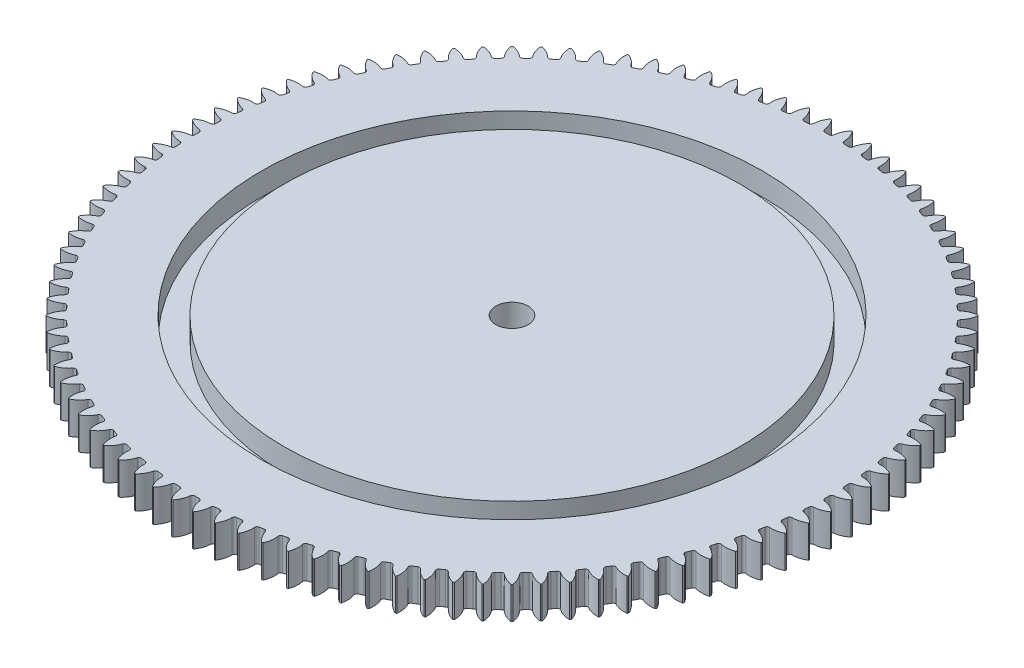
SolidWorks part; units mm, degrees
ref_plane "Front Plane" through (0, 0, 0) normal (0, 0, 1) x (1, 0, 0)
ref_plane "Top Plane" through (0, 0, 0) normal (0, 1, 0) x (1, 0, 0)
ref_plane "Right Plane" through (0, 0, 0) normal (1, 0, 0) x (0, 0, -1)
sketch "Sketch1" plane through (0, 0, 0) normal (0, 1, 0) x (1, 0, 0)
  circle A0 centre (0, 0) radius 5
  circle A1 centre (0, 0) radius 102
  dimension "D1" = 10
  dimension "D2" = 204
extrude "Boss-Extrude1" add sketch "Sketch1" along normal blind 10
sketch "Sketch2" plane through (0, 10, 0) normal (0, 1, 0) x (1, 0, 0)
  line L0 (0, 0) -> (0, 102) construction
  line L1 (-1.3895, 97.4901) -> (0, 0) construction
  line L2 (0, 94.8463) -> (-2.5918, 101.9671) construction
  circle A0 centre (0, 0) radius 102 construction
  arc A1 (1.3895, 97.4901) -> (-1.3895, 97.4901) centre (0, 0) ccw
  arc A2 (1.8707, 99.9825) -> (-1.8707, 99.9825) centre (0, 0) ccw construction
  arc A3 (3.0148, 101.9554) -> (-3.0148, 101.9554) centre (0, 0) ccw
  arc A4 (-3.0148, 101.9554) -> (-1.3895, 97.4901) centre (-8.6195, 97.387) cw
  arc A5 (3.0148, 101.9554) -> (1.3895, 97.4901) centre (8.6195, 97.387) ccw
  point P16 (-1.8249, 99.8601)
  dimension "D1" = 204
  dimension "D2" = 200
  dimension "D3" = 4.5
  dimension "D4" = 20
  dimension "D5" = 3.7416
extrude "Cut-Extrude1" cut sketch "Sketch2" against normal through all
fillet "Fillet1" radius 0.76 2 edges at (1.3895, 5, -97.4901) (-1.3895, 5, -97.4901)
pattern_circular "CirPattern2" count 100 over 360 about axis through (0, 10, 0) along (0, 1, 0) of "Cut-Extrude1", "Fillet1"
sketch "Sketch3" plane through (0, 10, 0) normal (0, 1, 0) x (1, 0, 0)
  circle A0 centre (0, 0) radius 73 construction
  circle A1 centre (0, 0) radius 77.5
  circle A2 centre (0, 0) radius 70.5
  dimension "D1" = 146
  dimension "D2" = 7
  dimension "D3" = 4.5
extrude "Cut-Extrude2" cut sketch "Sketch3" against normal blind 7
sketch "Sketch4" plane through (0, 0, 0) normal (0, -1, 0) x (1, 0, 0)
  circle A0 centre (0, 0) radius 100 construction
  dimension "D1" = 200
equation "\"Module\" = 2"
equation "\"No. of Teeth\"= 100"
equation "\"Bore Diameter\"= 10"
equation "\"Pressure Angle\"= 20deg"
equation "\"Outer Diameter\"= ( \"No. of Teeth\" + 2 ) * \"Module\""
equation "\"Pitch Diameter\"= \"No. of Teeth\" * \"Module\""
equation "\"Backlash\"= 0.3 * \"Module\""
equation "\"Arc Length\"= ( \"Module\" * pi ) / 2 + \"Backlash\""
equation "\"Fillet Radius\"= .38 * \"Module\""
equation "\"Tooth Depth\"= IIF ( \"Module\" <= 1.25 , 2.4 * \"Module\" , 2.25 * \"Module\" )"
equation "\"D1@Sketch1\"=\"Bore Diameter\""
equation "\"D2@Sketch1\"=\"Outer Diameter\""
equation "\"D2@Sketch2\"=\"Pitch Diameter\""
equation "\"D1@Sketch2\"=\"Outer Diameter\""
equation "\"D3@Sketch2\"=\"Tooth Depth\""
equation "\"D4@Sketch2\"=\"Pressure Angle\""
equation "\"D5@Sketch2\"=\"Arc Length\""
equation "\"D1@Fillet1\"=\"Fillet Radius\""
equation "\"D1@CirPattern2\"=\"No. of Teeth\""
equation "\"D1@Sketch4\"=\"Pitch Diameter\""
